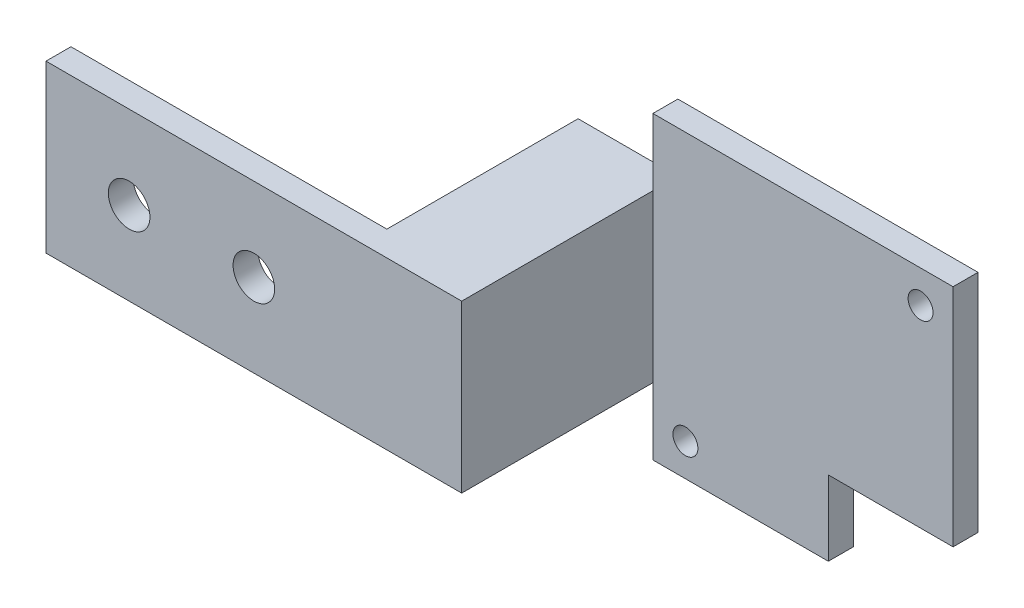
SolidWorks part; units mm, degrees
ref_plane "前视基准面" through (0, 0, 0) normal (0, 0, 1) x (1, 0, 0)
ref_plane "上视基准面" through (0, 0, 0) normal (0, 1, 0) x (1, 0, 0)
ref_plane "右视基准面" through (0, 0, 0) normal (1, 0, 0) x (0, 0, -1)
sketch "草图1" plane through (0, 0, 0) normal (0, 0, 1) x (1, 0, 0)
  line L1 (18.05, -18.05) -> (-18.05, -18.05)
  line L2 (18.05, -18.05) -> (18.05, 18.05)
  line L3 (18.05, 18.05) -> (-18.05, 18.05)
  line L4 (-18.05, -18.05) -> (-18.05, 18.05)
  line L5 (18.05, -18.05) -> (-18.05, 18.05) construction
  line L6 (18.05, 18.05) -> (-18.05, -18.05) construction
  point P0 (0, 0)
  dimension "D1" = 36.1
  dimension "D2" = 36.1
extrude "凸台-拉伸1" add sketch "草图1" along normal blind 3
sketch "草图2" plane through (0, 0, 3) normal (0, 0, 1) x (1, 0, 0)
  line L0 (0, 0) -> (14.1421, 14.1421) construction
  line L1 (0, 0) -> (18.05, -18.05) construction
  circle A0 centre (14.1421, 14.1421) radius 1.5
  circle A1 centre (-14.1421, -14.1421) radius 1.5
  dimension "D1" = 3
  dimension "D2" = 20
extrude "切除-拉伸1" cut sketch "草图2" against normal blind 3
sketch "草图3" plane through (0, 0, 3) normal (0, 0, 1) x (1, 0, 0)
  line L1 (18.05, -18.05) -> (3.05, -18.05)
  line L2 (18.05, -18.05) -> (18.05, -9.05)
  line L3 (18.05, -9.05) -> (3.05, -9.05)
  line L4 (3.05, -18.05) -> (3.05, -9.05)
  dimension "D1" = 15
  dimension "D2" = 9
extrude "切除-拉伸2" cut sketch "草图3" against normal blind 3
sketch "草图4" plane through (0, 0, 3) normal (0, 0, 1) x (1, 0, 0)
  line L0 (-18.05, 10) -> (-18.05, -10)
  line L1 (-18.05, 18.05) -> (-18.05, -18.05) construction
  line L2 (-18.05, -10) -> (-30.05, -10)
  line L3 (-30.05, -10) -> (-30.05, 10)
  line L4 (-30.05, 0) -> (-18.05, 0)
  line L5 (-18.05, 10) -> (-30.05, 10)
  line M7 (-18.05, 18.05) -> (-18.05, -18.05)
  dimension "D1" = 10
  dimension "D2" = 12
extrude "凸台-拉伸2" add sketch "草图4" against normal blind 3 contours L5 L3 L4 M7 | L4 L3 L2 L0 region at (-24.05, 5, 3) region at (-24.05, -5, 3)
sketch "草图5" plane through (0, 0, 3) normal (0, 0, 1) x (1, 0, 0)
  line L1 (-18.05, -10) -> (-30.05, -10)
  line L2 (-18.05, -10) -> (-18.05, 10)
  line L3 (-18.05, 10) -> (-30.05, 10)
  line L4 (-30.05, -10) -> (-30.05, 10)
  point P4 (-30.05, 8)
extrude "凸台-拉伸3" add sketch "草图5" along normal blind 20
sketch "草图7" plane through (0, 0, 23) normal (0, 0, 1) x (1, 0, 0)
  line L0 (-18.05, 10) -> (-30.05, 10) construction
  line L1 (-18.05, -10) -> (-68.05, -10)
  line L2 (-18.05, -10) -> (-18.05, 10)
  line L3 (-18.05, 10) -> (-68.05, 10)
  line L4 (-68.05, -10) -> (-68.05, 10)
  dimension "D1" = 50
extrude "凸台-拉伸4" add sketch "草图7" along normal blind 3
sketch "草图9" plane through (0, 0, 26) normal (0, 0, 1) x (1, 0, 0)
  line L0 (-68.05, 10) -> (-68.05, -10) construction
  circle A0 centre (-58.05, 0) radius 2.5
  circle A1 centre (-43.05, 0) radius 2.5
  dimension "D1" = 10
  dimension "D2" = 15
  dimension "D3" = 5
  dimension "D4" = 5
extrude "切除-拉伸4" cut sketch "草图9" against normal blind 3
